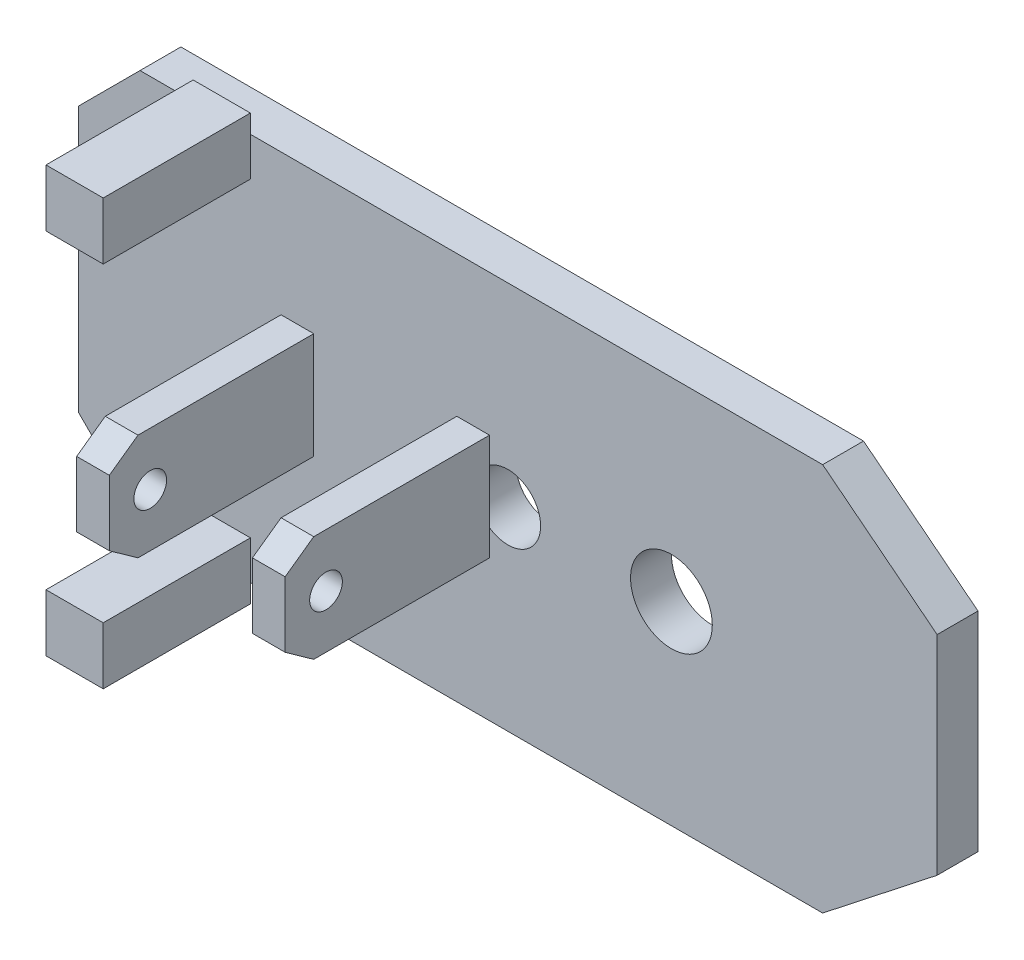
SolidWorks part; units mm, degrees
ref_plane "Front Plane" through (0, 0, 0) normal (0, 0, 1) x (1, 0, 0)
ref_plane "Top Plane" through (0, 0, 0) normal (0, 1, 0) x (1, 0, 0)
ref_plane "Right Plane" through (0, 0, 0) normal (1, 0, 0) x (0, 0, -1)
ref_plane "PL_Sole_Plate_base" through (0, 0, -50) normal (0, 0, 1) x (1, 0, 0)
sketch "SK_Sole_Plate" plane through (0, 0, -50) normal (0, 0, 1) x (1, 0, 0)
  line L0 (-60, 47.5) -> (107, 47.5)
  line L1 (107, 47.5) -> (135, 25.5)
  line L2 (135, 25.5) -> (135, -25.5)
  line L3 (135, -25.5) -> (107, -47.5)
  line L4 (107, -47.5) -> (-60, -47.5)
  line L5 (-60, -47.5) -> (-75, -32.5)
  line L6 (-75, -32.5) -> (-75, 32.5)
  line L7 (-75, 32.5) -> (-60, 47.5)
  circle A0 centre (70, 0) radius 10
  circle A1 centre (30, 0) radius 8
  dimension "D17_SK_Sole_Plate" = 20
  dimension "D19_SK_Sole_Plate" = 16
  dimension "P1" = 60
  dimension "P2" = 47.5
  dimension "P3" = 107
  dimension "P4" = 47.5
  dimension "P5" = 135
  dimension "P6" = 25.5
  dimension "P7" = 135
  dimension "P8" = 25.5
  dimension "P9" = 107
  dimension "P10" = 47.5
  dimension "P11" = 60
  dimension "P12" = 47.5
  dimension "P13" = 75
  dimension "P14" = 32.5
  dimension "P15" = 75
  dimension "P16" = 32.5
  dimension "P18" = 70
  dimension "P20" = 30
extrude "Sole_Plate" add sketch "SK_Sole_Plate" along normal blind 10
ref_plane "PL_Clevis_Front_base" through (17.5, 0, 0) normal (1, 0, 0) x (0, 0, -1)
sketch "SK_Clevis_Front" plane through (17.5, 0, 0) normal (1, 0, 0) x (0, 0, -1)
  line L0 (40, 13) -> (40, -13)
  line L1 (40, -13) -> (-3, -13)
  line L2 (-3, -13) -> (-10, -8)
  line L3 (-10, -8) -> (-10, 8)
  line L4 (-10, 8) -> (-3, 13)
  line L5 (-3, 13) -> (40, 13)
  circle A0 centre (0, 0) radius 4
  dimension "D13_SK_Clevis_Front" = 8
  dimension "P1" = 40
  dimension "P2" = 13
  dimension "P3" = 40
  dimension "P4" = 13
  dimension "P5" = 3
  dimension "P6" = 13
  dimension "P7" = 10
  dimension "P8" = 8
  dimension "P9" = 10
  dimension "P10" = 8
  dimension "P11" = 3
  dimension "P12" = 13
extrude "Clevis_Front" add sketch "SK_Clevis_Front" along normal blind 8
ref_plane "PL_Clevis_Back_base" through (-25.5, 0, 0) normal (1, 0, 0) x (0, 0, -1)
sketch "SK_Clevis_Back" plane through (-25.5, 0, 0) normal (1, 0, 0) x (0, 0, -1)
  line L0 (40, 13) -> (40, -13)
  line L1 (40, -13) -> (-3, -13)
  line L2 (-3, -13) -> (-10, -8)
  line L3 (-10, -8) -> (-10, 8)
  line L4 (-10, 8) -> (-3, 13)
  line L5 (-3, 13) -> (40, 13)
  circle A0 centre (0, 0) radius 4
  dimension "D13_SK_Clevis_Back" = 8
  dimension "P1" = 40
  dimension "P2" = 13
  dimension "P3" = 40
  dimension "P4" = 13
  dimension "P5" = 3
  dimension "P6" = 13
  dimension "P7" = 10
  dimension "P8" = 8
  dimension "P9" = 10
  dimension "P10" = 8
  dimension "P11" = 3
  dimension "P12" = 13
extrude "Clevis_Back" add sketch "SK_Clevis_Back" along normal blind 8
ref_plane "PL_Post_Lat_base" through (0, 0, -40) normal (0, 0, 1) x (1, 0, 0)
sketch "SK_Post_Lat" plane through (0, 0, -40) normal (0, 0, 1) x (1, 0, 0)
  line L0 (-47, -38) -> (-33, -38)
  line L1 (-33, -38) -> (-33, -52)
  line L2 (-33, -52) -> (-47, -52)
  line L3 (-47, -52) -> (-47, -38)
  dimension "P1" = 47
  dimension "P2" = 38
  dimension "P3" = 33
  dimension "P4" = 38
  dimension "P5" = 33
  dimension "P6" = 52
  dimension "P7" = 47
  dimension "P8" = 52
extrude "Post_Lat" add sketch "SK_Post_Lat" along normal blind 36
ref_plane "PL_Post_Med_base" through (0, 0, -40) normal (0, 0, 1) x (1, 0, 0)
sketch "SK_Post_Med" plane through (0, 0, -40) normal (0, 0, 1) x (1, 0, 0)
  line L0 (-47, 52) -> (-33, 52)
  line L1 (-33, 52) -> (-33, 38)
  line L2 (-33, 38) -> (-47, 38)
  line L3 (-47, 38) -> (-47, 52)
  dimension "P1" = 47
  dimension "P2" = 52
  dimension "P3" = 33
  dimension "P4" = 52
  dimension "P5" = 33
  dimension "P6" = 38
  dimension "P7" = 47
  dimension "P8" = 38
extrude "Post_Med" add sketch "SK_Post_Med" along normal blind 36
ref_axis "AX_Roll" through (-85.5, 0, 0) along (1, 0, 0)
sketch "SK_RodBalls" plane through (0, 0, 0) normal (0, 0, 1) x (1, 0, 0)
  point P0 (-40, -45)
  point P2 (-40, 45)
  dimension "P1" = 40
  dimension "P2" = 45
  dimension "P3" = 40
  dimension "P4" = 45
equation "\"Foot_length\" = 210"
equation "\"Foot_width\" = 95"
equation "\"Ankle_height\" = 50"
